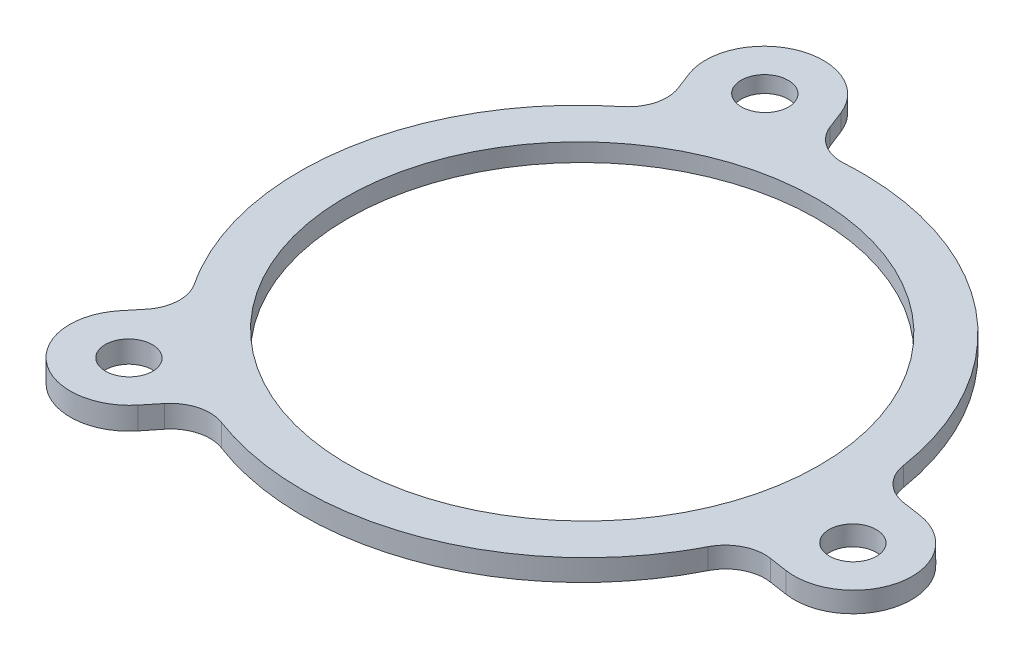
SolidWorks part; units mm, degrees
material "5454-O"
ref_plane "Front Plane" through (0, 0, 0) normal (0, 0, 1) x (1, 0, 0)
ref_plane "Top Plane" through (0, 0, 0) normal (0, 1, 0) x (1, 0, 0)
ref_plane "Right Plane" through (0, 0, 0) normal (1, 0, 0) x (0, 0, -1)
sketch "Sketch1" plane through (0, 0, 0) normal (0, 0, 1) x (1, 0, 0)
  line L0 (-3.7459, 1) -> (5.6477, 1) construction
  dimension "D1" = 1
ref_plane "Plane1" through (0, 0.9999, -0.0099) normal (0, 1, -0.0099) x (1, 0, 0)
sketch "Sketch2" plane through (0, 0, 0) normal (0, 1, 0) x (1, 0, 0)
  line L0 (0, 0) -> (-6.0205, 15.3624) construction
  line L1 (0, 0) -> (-10.294, -12.8951) construction
  line L2 (0, 0) -> (16.3145, -2.4673) construction
  line L3 (-6.0205, 15.3624) -> (-3.2273, 16.4571) construction
  line L4 (-6.0205, 15.3624) -> (-8.8136, 14.2678) construction
  line L5 (-3.2273, 16.4571) -> (-2.3151, 14.1294) construction
  line L6 (-8.8136, 14.2678) -> (-7.9014, 11.9402) construction
  line L7 (16.3145, -2.4673) -> (16.7631, 0.4989) construction
  line L8 (16.3145, -2.4673) -> (15.8659, -5.4336) construction
  line L9 (16.7631, 0.4989) -> (14.2912, 0.8728) construction
  line L10 (15.8659, -5.4336) -> (13.394, -5.0598) construction
  line L11 (-10.294, -12.8951) -> (-7.9495, -14.7667) construction
  line L12 (-10.294, -12.8951) -> (-12.6386, -11.0234) construction
  line L13 (-12.6386, -11.0234) -> (-11.0789, -9.0696) construction
  line L14 (-7.9495, -14.7667) -> (-6.3898, -12.8129) construction
  line L15 (-8.8136, 14.2678) -> (-8.4608, 13.3674)
  line L16 (-3.2273, 16.4571) -> (-2.8744, 15.5566)
  line L17 (16.7631, 0.4989) -> (15.8069, 0.6436)
  line L18 (15.8659, -5.4336) -> (14.9097, -5.289)
  line L19 (-7.9495, -14.7667) -> (-7.3461, -14.0109)
  line L20 (-12.6386, -11.0234) -> (-12.0352, -10.2676)
  arc A0 (-8.8136, 14.2678) -> (-3.2273, 16.4571) centre (-6.0205, 15.3624) cw
  arc A1 (16.7631, 0.4989) -> (15.8659, -5.4336) centre (16.3145, -2.4673) cw
  arc A2 (-7.9495, -14.7667) -> (-12.6386, -11.0234) centre (-10.294, -12.8951) cw
  arc A3 (-0.8882, 14.2902) -> (14.1319, 2.2998) centre (0, 0) cw
  arc A4 (12.8198, -6.3759) -> (-5.0743, -13.3885) centre (0, 0) cw
  arc A5 (-11.9316, -7.9144) -> (-9.0576, 11.0887) centre (0, 0) cw
  arc A6 (-11.9316, -7.9144) -> (-12.0352, -10.2676) centre (-13.5983, -9.0199) cw
  arc A7 (12.8198, -6.3759) -> (14.9097, -5.289) centre (14.6106, -7.2665) cw
  arc A8 (-0.8882, 14.2902) -> (-2.8744, 15.5566) centre (-1.0123, 16.2864) cw
  arc A9 (-7.3461, -14.0109) -> (-5.0743, -13.3885) centre (-5.7831, -15.2587) cw
  arc A10 (15.8069, 0.6436) -> (14.1319, 2.2998) centre (16.1059, 2.6211) cw
  arc A11 (-9.0576, 11.0887) -> (-8.4608, 13.3674) centre (-10.3229, 12.6376) ccw
  circle A12 centre (0, 0) radius 12
  circle A13 centre (-6.0205, 15.3624) radius 1.2
  circle A14 centre (16.3145, -2.4673) radius 1.2
  circle A15 centre (-10.294, -12.8951) radius 1.2
  dimension "D1" = 2
  dimension "D2" = 2
extrude "Boss-Extrude1" add sketch "Sketch2" along normal up to surface (0.8581 mm away) up to plane "Plane1"
sketch3d "3DSketch2"
  point P0 (20.3145, 1.4981, -19.3624)
